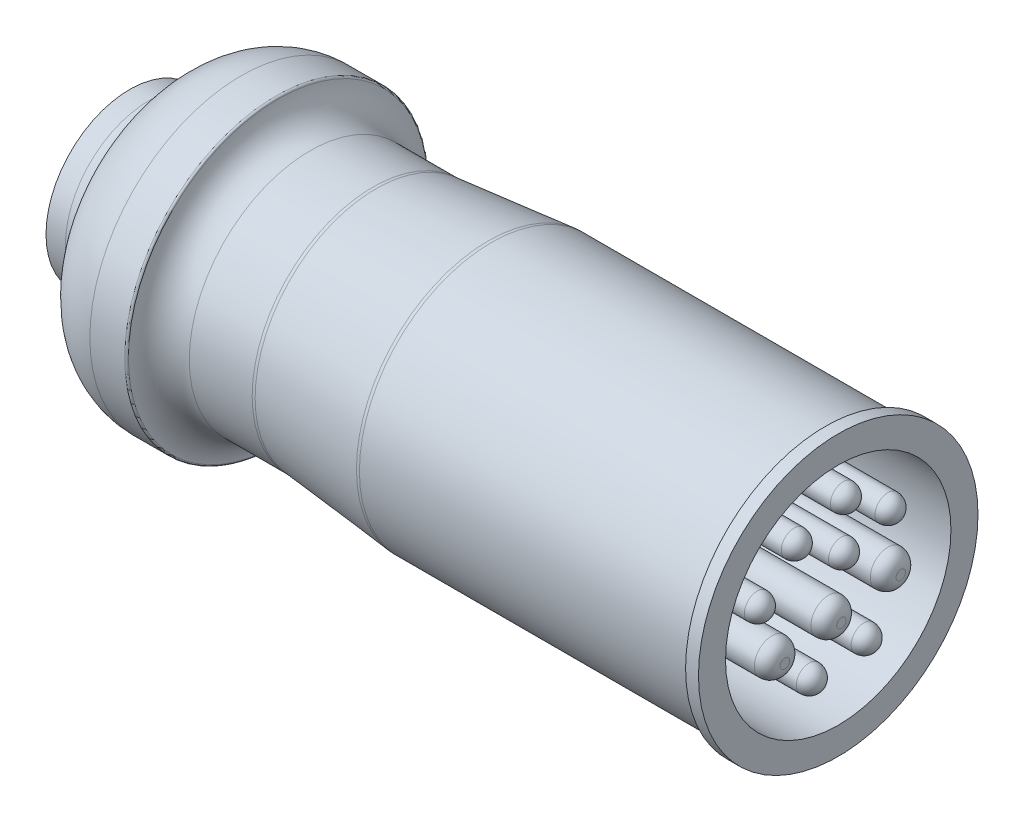
SolidWorks part; units mm, degrees
ref_plane "Front Plane" through (0, 0, 0) normal (0, 0, 1) x (1, 0, 0)
ref_plane "Top Plane" through (0, 0, 0) normal (0, 1, 0) x (1, 0, 0)
ref_plane "Right Plane" through (0, 0, 0) normal (1, 0, 0) x (0, 0, -1)
sketch "Sketch3" plane through (0, 0, 0) normal (0, 0, 1) x (1, 0, 0)
  line L0 (0, 0) -> (0, -50000) construction
  line L1 (0, 0) -> (50000, 0) construction
  line L2 (65, 0) -> (65, 20.5)
  line L3 (65, 17.5) -> (11.0609, 17.5) construction
  line L4 (11.0609, 17.5) -> (-6.8538, 15.75) construction
  line L5 (-6.8538, 15.75) -> (-25, 15.75) construction
  line L6 (-25, 15.75) -> (-25, 20.5) construction
  line L7 (-42, 0) -> (-42, 53.8042) construction
  line L8 (-25, 20.5) -> (-27.6909, 20.5) construction
  line L9 (-42, 10) -> (-43.4514, 10) construction
  line L10 (-42, 13) -> (-42, 0) construction
  line L11 (-42, 0) -> (65, 0)
  line L12 (65, 20.5) -> (10.9147, 20.5)
  line L13 (10.9147, 20.5) -> (-7, 18.75)
  line L14 (-7, 18.75) -> (-22, 18.75)
  line L15 (-22, 18.75) -> (-22, 23.5)
  line L16 (-22, 23.5) -> (-27.6909, 23.5)
  line L17 (-42, 13) -> (-45, 13)
  line L18 (-45, 13) -> (-45, 0)
  line L19 (-45, 0) -> (-42, 0)
  arc A0 (-42, 10) -> (-35.3224, 14.9) centre (-42, 17) ccw construction
  arc A1 (-35.3224, 14.9) -> (-27.6909, 20.5) centre (-27.6909, 12.5) cw construction
  arc A2 (-38.1842, 15.8) -> (-27.6909, 23.5) centre (-27.6909, 12.5) cw
  arc A3 (-42, 13) -> (-38.1842, 15.8) centre (-42, 17) ccw
  point P29 (-29.5214, 23.5)
  point P31 (-17.7271, 18.75)
  point P32 (0, 0)
  point P34 (0, 0)
  point P35 (0, 0)
  point P36 (5.7542, 20.5)
  point P37 (-11.4039, 18.75)
  point P38 (2.5448, 20.5)
  point P39 (4.5198, 20.5)
  dimension "D8" = 20
  dimension "D9" = 7
  dimension "D10" = 8
  dimension "D1" = 17.5
  dimension "D2" = 23
  dimension "D3" = 18
  dimension "D4" = 15.75
  dimension "D5" = 41
  dimension "D6" = 110
  dimension "D7" = 3
  dimension "D11" = 3
  dimension "D12" = 45
  dimension "D13" = 15
revolve "Revolve1" add sketch "Sketch3" angle 360 about L1
fillet "Fillet1" radius 5 1 edges at (-22, 0, 18.75)
fillet "Fillet2" radius 0.3 1 edges at (-22, 0, 23.5)
fillet "Fillet3" radius 5 2 edges at (10.9147, 0, 20.5) (-7, 0, 18.75)
sketch "Sketch4" plane through (65, 0, 0) normal (1, 0, 0) x (0, 0, -1)
  circle A2 centre (0, 0) radius 17.5
  circle A3 centre (0, 0) radius 17.5
  dimension "D1" = 3
extrude "Cut-Extrude1" cut sketch "Sketch4" against normal blind 35
sketch "Sketch5" plane through (30, 0, 0) normal (1, 0, 0) x (0, 0, -1)
  line L0 (0, 0) -> (0, -50000) construction
  line L1 (0, 0) -> (50000, 0) construction
  circle A0 centre (2.4852, 3.5673) radius 2.0006
  circle A1 centre (2.7845, 10.8694) radius 2.0006
  circle A2 centre (-4.8439, 8.4442) radius 2.0006
  circle A3 centre (-10.5763, 2.8441) radius 2.0006
  circle A4 centre (9.7074, 5.9308) radius 2.0006
  circle A5 centre (-2.5069, -10.8694) radius 2.0006
  circle A6 centre (6.0034, -9.7229) radius 2.0006
  circle A7 centre (9.7074, -2.1386) radius 2.7332
  circle A8 centre (0.4915, -3.9906) radius 2.7332
  circle A9 centre (-8.2833, -5.0489) radius 2.7332
extrude "Boss-Extrude1" add sketch "Sketch5" along normal up to surface (35 mm away) up to face at (65, 0, -17.5)
fillet "Fillet4" radius 2 10 edges at (65, -10.8694, 4.5075) (65, -9.7229, -4.0028) (65, -2.1386, -6.9742) (65, -3.9906, 2.2416) (65, -5.0489, 11.0165) (65, 2.8441, 12.5769) (65, 3.5673, -0.4846) (65, 5.9308, -7.7068) (65, 10.8694, -0.7839) (65, 8.4442, 6.8446)
sketch "Sketch6" plane through (65, 0, 0) normal (1, 0, 0) x (0, 0, -1)
  circle A0 centre (0, 0) radius 20.5 construction
  circle A1 centre (0, 0) radius 20.5
  circle A2 centre (0, 0) radius 21.7
  dimension "D1" = 1.2
extrude "Boss-Extrude2" add sketch "Sketch6" against normal blind 2
